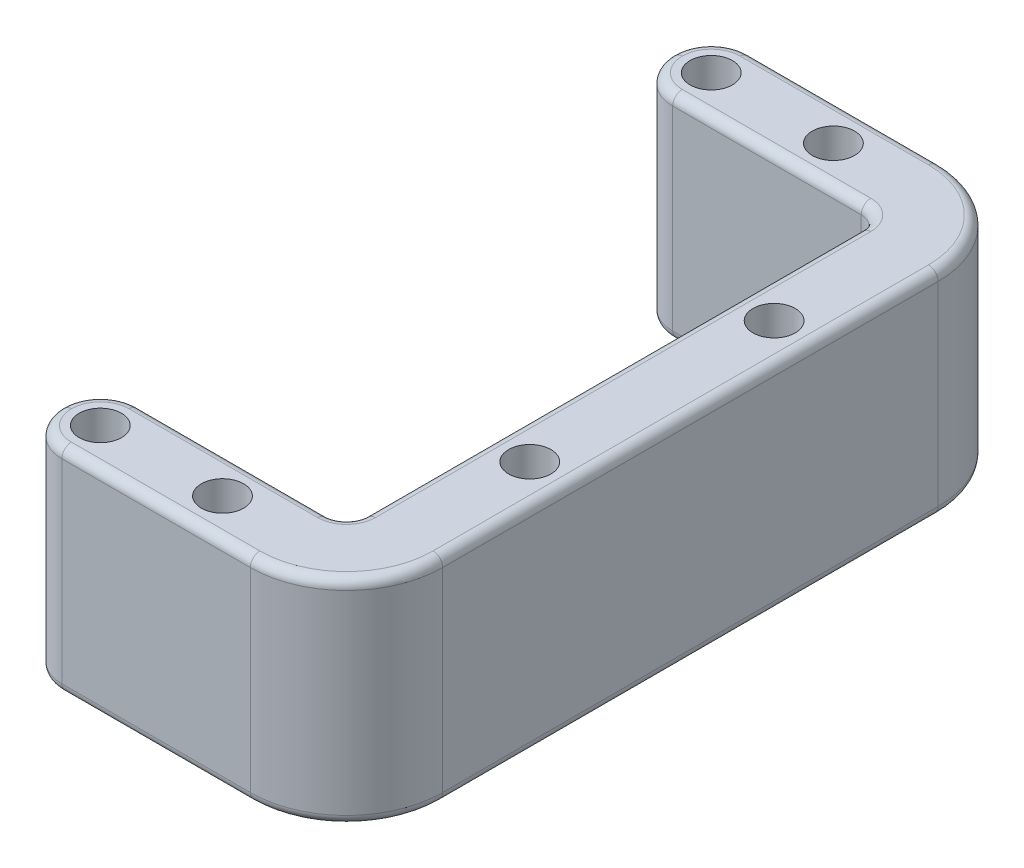
SolidWorks part; units mm, degrees
ref_plane "Front Plane" through (0, 0, 0) normal (0, 0, 1) x (1, 0, 0)
ref_plane "Top Plane" through (0, 0, 0) normal (0, 1, 0) x (1, 0, 0)
ref_plane "Right Plane" through (0, 0, 0) normal (1, 0, 0) x (0, 0, -1)
sketch "Sketch1" plane through (0, 0, 0) normal (0, 1, 0) x (1, 0, 0)
  line L1 (-4, 4) -> (21.59, 4)
  line L2 (-4, 4) -> (-4, -4)
  line L3 (-4, -4) -> (29.59, -4)
  line L5 (29.59, -4) -> (19.8585, -4)
  line L8 (21.59, 4) -> (21.59, 59.5)
  line L9 (29.59, 67.5) -> (-4, 67.5)
  line L10 (29.59, 67.5) -> (29.59, -4)
  line L11 (21.59, 59.5) -> (-4, 59.5)
  line L12 (-4, 67.5) -> (-4, 59.5)
  circle A0 centre (0, 0) radius 2.2
  circle A1 centre (12.7, 0) radius 2.2
  circle A2 centre (12.7, 63.5) radius 2.2
  circle A3 centre (0, 63.5) radius 2.2
  circle A4 centre (25.59, 44.45) radius 2.2
  circle A5 centre (25.59, 19.05) radius 2.2
  point P9 (-4, 63.5)
  point P19 (21.59, 59.5)
  point P20 (21.59, 4)
  point P24 (21.59, 31.75)
  point P27 (-4, 0)
  dimension "D1" = 4.4
  dimension "D11" = 4
  dimension "D2" = 12.7
  dimension "D3" = 63.5
  dimension "D4" = 8
  dimension "D5" = 8
  dimension "D6" = 8
  dimension "D7" = 4
  dimension "D8" = 8.89
  dimension "D9" = 25.4
  dimension "D10" = 12.7
extrude "Boss-Extrude1" add sketch "Sketch1" along normal blind 22.2504 contours L9 L12 L11 L8 L1 L2 L3 L10 A3 A2 A1 A0 region at (8.795, 0, -3.21)
fillet "Fillet1" radius 10 2 edges at (29.59, 11.1252, -67.5) (29.59, 11.1252, 4)
fillet "Fillet2" radius 2 2 edges at (21.59, 11.1252, -59.5) (21.59, 11.1252, -4)
fillet "Fillet3" radius 4 4 edges at (-4, 11.1252, -67.5) (-4, 11.1252, -59.5) (-4, 11.1252, -4) (-4, 11.1252, 4)
fillet "Fillet4" radius 1 28 edges at (-2.8284, 0, 2.8284) (-2.8284, 0, -2.8284) (9.795, 0, -4) (21.0042, 0, -4.5858) (21.59, 0, -31.75) (21.0042, 0, -58.9142) (9.795, 0, -59.5) (-2.8284, 0, -60.6716) (-2.8284, 0, -66.3284) (9.795, 0, -67.5) (26.6611, 0, -64.5711) (29.59, 0, -31.75) (26.6611, 0, 1.0711) (-2.8284, 22.2504, 2.8284) (-2.8284, 22.2504, -2.8284) (9.795, 22.2504, -4) (21.0042, 22.2504, -4.5858) (21.59, 22.2504, -31.75) (21.0042, 22.2504, -58.9142) (9.795, 22.2504, -59.5) (-2.8284, 22.2504, -60.6716) (-2.8284, 22.2504, -66.3284) (9.795, 22.2504, -67.5) (26.6611, 22.2504, -64.5711) (29.59, 22.2504, -31.75) (26.6611, 22.2504, 1.0711) (9.795, 0, 4) (9.795, 22.2504, 4)
